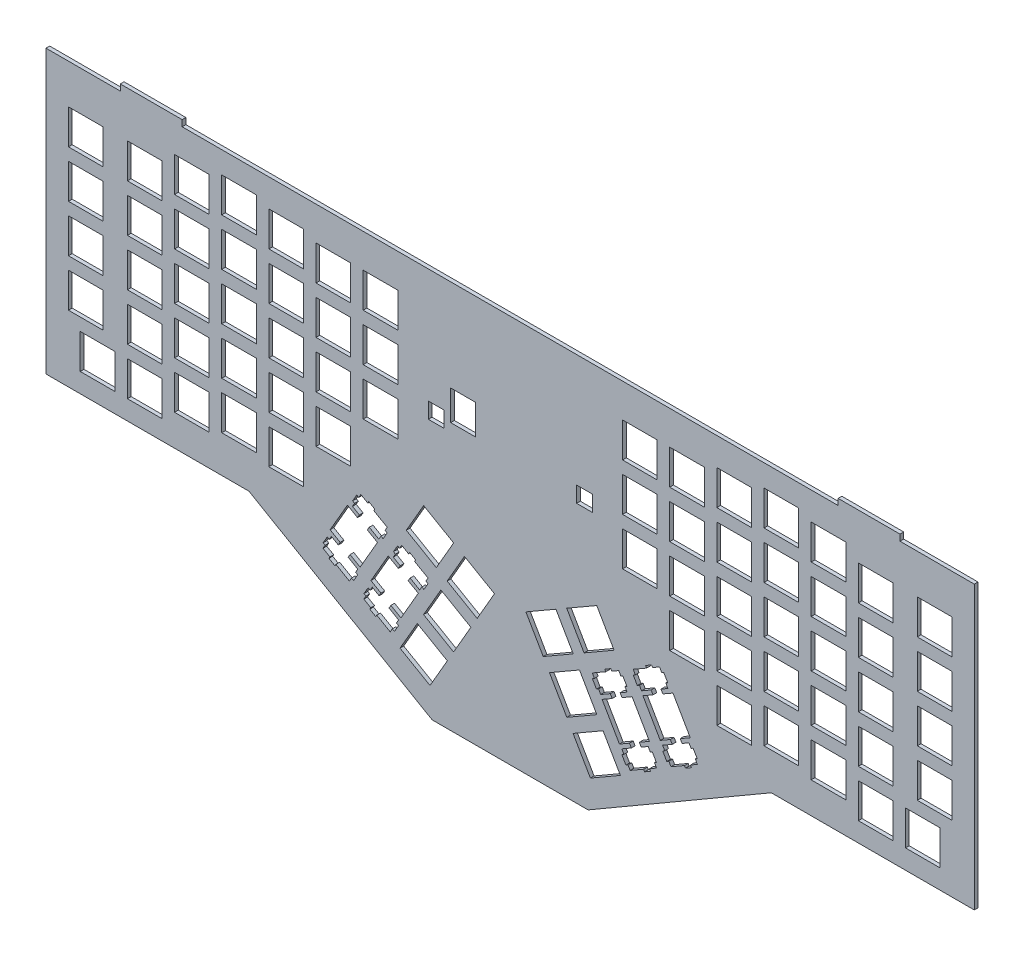
SolidWorks part; units mm, degrees
ref_plane "Front Plane" through (0, 0, 0) normal (0, 0, 1) x (1, 0, 0)
ref_plane "Top Plane" through (0, 0, 0) normal (0, 1, 0) x (1, 0, 0)
ref_plane "Right Plane" through (0, 0, 0) normal (1, 0, 0) x (0, 0, -1)
sketch "Model" plane through (0, 0, 0) normal (0, 0, 1) x (1, 0, 0)
  line L0 (0.0951, 142.78) -> (371.57, 142.78)
  line L1 (371.57, 142.78) -> (371.57, 0.2467)
  line L2 (371.57, 0.2467) -> (0.0951, 0.2467)
  line L3 (0.0951, 0.2467) -> (0.0951, 142.78)
  line L4 (141.314, 10.6977) -> (153.439, 3.6973)
  line L5 (153.439, 3.6973) -> (160.438, 15.8213)
  line L6 (160.438, 15.8213) -> (148.314, 22.8217)
  line L7 (148.314, 22.8217) -> (141.314, 10.6977)
  line L8 (211.224, 15.8213) -> (218.225, 3.6973)
  line L9 (218.225, 3.6973) -> (230.35, 10.6977)
  line L10 (230.35, 10.6977) -> (223.35, 22.8217)
  line L11 (223.35, 22.8217) -> (211.224, 15.8213)
  line L12 (141.126, 45.533) -> (140.33, 45.992)
  line L13 (140.33, 45.992) -> (138.679, 43.1341)
  line L14 (138.679, 43.1341) -> (139.477, 42.6752)
  line L15 (139.477, 42.6752) -> (138.614, 41.1812)
  line L16 (138.614, 41.1812) -> (141.412, 39.5661)
  line L17 (141.412, 39.5661) -> (140.648, 38.2461)
  line L18 (140.648, 38.2461) -> (136.579, 40.5955)
  line L19 (136.579, 40.5955) -> (129.578, 28.4716)
  line L20 (129.578, 28.4716) -> (133.649, 26.1221)
  line L21 (133.649, 26.1221) -> (132.887, 24.8006)
  line L22 (132.887, 24.8006) -> (130.09, 26.4156)
  line L23 (130.09, 26.4156) -> (129.227, 24.9218)
  line L24 (129.227, 24.9218) -> (128.429, 25.3821)
  line L25 (128.429, 25.3821) -> (126.78, 22.524)
  line L26 (126.78, 22.524) -> (127.576, 22.0638)
  line L27 (127.576, 22.0638) -> (126.715, 20.57)
  line L28 (126.715, 20.57) -> (129.512, 18.9549)
  line L29 (129.512, 18.9549) -> (129.099, 18.2411)
  line L30 (129.099, 18.2411) -> (131.524, 16.841)
  line L31 (131.524, 16.841) -> (131.936, 17.5548)
  line L32 (131.936, 17.5548) -> (137.367, 14.4198)
  line L33 (137.367, 14.4198) -> (138.228, 15.9136)
  line L34 (138.228, 15.9136) -> (139.077, 15.423)
  line L35 (139.077, 15.423) -> (140.728, 18.2811)
  line L36 (140.728, 18.2811) -> (139.879, 18.773)
  line L37 (139.879, 18.773) -> (140.742, 20.2654)
  line L38 (140.742, 20.2654) -> (136.871, 22.5006)
  line L39 (136.871, 22.5006) -> (137.633, 23.8221)
  line L40 (137.633, 23.8221) -> (141.702, 21.4712)
  line L41 (141.702, 21.4712) -> (148.703, 33.5952)
  line L42 (148.703, 33.5952) -> (144.632, 35.9463)
  line L43 (144.632, 35.9463) -> (145.396, 37.2664)
  line L44 (145.396, 37.2664) -> (149.266, 35.0311)
  line L45 (149.266, 35.0311) -> (150.129, 36.5248)
  line L46 (150.129, 36.5248) -> (150.978, 36.0345)
  line L47 (150.978, 36.0345) -> (152.628, 38.8923)
  line L48 (152.628, 38.8923) -> (151.778, 39.3831)
  line L49 (151.778, 39.3831) -> (152.641, 40.8767)
  line L50 (152.641, 40.8767) -> (147.212, 44.0119)
  line L51 (147.212, 44.0119) -> (147.624, 44.7269)
  line L52 (147.624, 44.7269) -> (145.198, 46.1271)
  line L53 (145.198, 46.1271) -> (144.786, 45.412)
  line L54 (144.786, 45.412) -> (141.989, 47.027)
  line L55 (141.989, 47.027) -> (141.126, 45.533)
  line L56 (226.876, 45.412) -> (226.464, 46.1271)
  line L57 (226.464, 46.1271) -> (224.04, 44.7269)
  line L58 (224.04, 44.7269) -> (224.452, 44.0119)
  line L59 (224.452, 44.0119) -> (219.021, 40.8767)
  line L60 (219.021, 40.8767) -> (219.884, 39.3831)
  line L61 (219.884, 39.3831) -> (219.035, 38.8923)
  line L62 (219.035, 38.8923) -> (220.686, 36.0345)
  line L63 (220.686, 36.0345) -> (221.535, 36.5248)
  line L64 (221.535, 36.5248) -> (222.396, 35.0311)
  line L65 (222.396, 35.0311) -> (226.267, 37.2664)
  line L66 (226.267, 37.2664) -> (227.031, 35.9463)
  line L67 (227.031, 35.9463) -> (222.961, 33.5952)
  line L68 (222.961, 33.5952) -> (229.96, 21.4712)
  line L69 (229.96, 21.4712) -> (234.031, 23.8221)
  line L70 (234.031, 23.8221) -> (234.793, 22.5006)
  line L71 (234.793, 22.5006) -> (230.922, 20.2654)
  line L72 (230.922, 20.2654) -> (231.785, 18.773)
  line L73 (231.785, 18.773) -> (230.936, 18.2811)
  line L74 (230.936, 18.2811) -> (232.585, 15.423)
  line L75 (232.585, 15.423) -> (233.434, 15.9136)
  line L76 (233.434, 15.9136) -> (234.297, 14.4198)
  line L77 (234.297, 14.4198) -> (239.726, 17.5548)
  line L78 (239.726, 17.5548) -> (240.14, 16.841)
  line L79 (240.14, 16.841) -> (242.565, 18.2411)
  line L80 (242.565, 18.2411) -> (242.152, 18.9549)
  line L81 (242.152, 18.9549) -> (244.949, 20.57)
  line L82 (244.949, 20.57) -> (244.086, 22.0638)
  line L83 (244.086, 22.0638) -> (244.883, 22.524)
  line L84 (244.883, 22.524) -> (243.233, 25.3821)
  line L85 (243.233, 25.3821) -> (242.437, 24.9218)
  line L86 (242.437, 24.9218) -> (241.573, 26.4156)
  line L87 (241.573, 26.4156) -> (238.777, 24.8006)
  line L88 (238.777, 24.8006) -> (238.014, 26.1221)
  line L89 (238.014, 26.1221) -> (242.084, 28.4716)
  line L90 (242.084, 28.4716) -> (235.085, 40.5955)
  line L91 (235.085, 40.5955) -> (231.014, 38.2461)
  line L92 (231.014, 38.2461) -> (230.251, 39.5661)
  line L93 (230.251, 39.5661) -> (233.048, 41.1812)
  line L94 (233.048, 41.1812) -> (232.187, 42.6752)
  line L95 (232.187, 42.6752) -> (232.984, 43.1341)
  line L96 (232.984, 43.1341) -> (231.334, 45.992)
  line L97 (231.334, 45.992) -> (230.536, 45.533)
  line L98 (230.536, 45.533) -> (229.674, 47.027)
  line L99 (229.674, 47.027) -> (226.876, 45.412)
  line L100 (150.839, 27.1942) -> (162.964, 20.1952)
  line L101 (162.964, 20.1952) -> (169.963, 32.3191)
  line L102 (169.963, 32.3191) -> (157.839, 39.3196)
  line L103 (157.839, 39.3196) -> (150.839, 27.1942)
  line L104 (201.699, 32.3191) -> (208.7, 20.1952)
  line L105 (208.7, 20.1952) -> (220.825, 27.1942)
  line L106 (220.825, 27.1942) -> (213.825, 39.3196)
  line L107 (213.825, 39.3196) -> (201.699, 32.3191)
  line L108 (124.627, 55.058) -> (123.832, 55.517)
  line L109 (123.832, 55.517) -> (122.182, 52.6591)
  line L110 (122.182, 52.6591) -> (122.979, 52.2002)
  line L111 (122.979, 52.2002) -> (122.116, 50.7062)
  line L112 (122.116, 50.7062) -> (124.912, 49.0911)
  line L113 (124.912, 49.0911) -> (124.15, 47.7711)
  line L114 (124.15, 47.7711) -> (120.081, 50.1206)
  line L115 (120.081, 50.1206) -> (113.08, 37.9966)
  line L116 (113.08, 37.9966) -> (117.151, 35.6471)
  line L117 (117.151, 35.6471) -> (116.389, 34.3256)
  line L118 (116.389, 34.3256) -> (113.592, 35.9406)
  line L119 (113.592, 35.9406) -> (112.729, 34.4468)
  line L120 (112.729, 34.4468) -> (111.933, 34.9071)
  line L121 (111.933, 34.9071) -> (110.283, 32.0491)
  line L122 (110.283, 32.0491) -> (111.078, 31.5888)
  line L123 (111.078, 31.5888) -> (110.217, 30.095)
  line L124 (110.217, 30.095) -> (113.013, 28.4799)
  line L125 (113.013, 28.4799) -> (112.601, 27.7661)
  line L126 (112.601, 27.7661) -> (115.025, 26.366)
  line L127 (115.025, 26.366) -> (115.438, 27.0798)
  line L128 (115.438, 27.0798) -> (120.869, 23.9448)
  line L129 (120.869, 23.9448) -> (121.731, 25.4386)
  line L130 (121.731, 25.4386) -> (122.579, 24.948)
  line L131 (122.579, 24.948) -> (124.229, 27.806)
  line L132 (124.229, 27.806) -> (123.38, 28.2966)
  line L133 (123.38, 28.2966) -> (124.244, 29.7904)
  line L134 (124.244, 29.7904) -> (120.373, 32.0256)
  line L135 (120.373, 32.0256) -> (121.135, 33.3471)
  line L136 (121.135, 33.3471) -> (125.204, 30.9962)
  line L137 (125.204, 30.9962) -> (132.205, 43.12)
  line L138 (132.205, 43.12) -> (128.134, 45.4713)
  line L139 (128.134, 45.4713) -> (128.898, 46.7914)
  line L140 (128.898, 46.7914) -> (132.769, 44.5562)
  line L141 (132.769, 44.5562) -> (133.631, 46.0498)
  line L142 (133.631, 46.0498) -> (134.48, 45.5595)
  line L143 (134.48, 45.5595) -> (136.13, 48.4173)
  line L144 (136.13, 48.4173) -> (135.281, 48.9081)
  line L145 (135.281, 48.9081) -> (136.143, 50.4017)
  line L146 (136.143, 50.4017) -> (130.714, 53.5368)
  line L147 (130.714, 53.5368) -> (131.126, 54.2519)
  line L148 (131.126, 54.2519) -> (128.702, 55.6521)
  line L149 (128.702, 55.6521) -> (128.288, 54.937)
  line L150 (128.288, 54.937) -> (125.491, 56.552)
  line L151 (125.491, 56.552) -> (124.627, 55.058)
  line L152 (243.374, 54.937) -> (242.962, 55.6521)
  line L153 (242.962, 55.6521) -> (240.538, 54.2519)
  line L154 (240.538, 54.2519) -> (240.95, 53.5368)
  line L155 (240.95, 53.5368) -> (235.519, 50.4017)
  line L156 (235.519, 50.4017) -> (236.383, 48.9081)
  line L157 (236.383, 48.9081) -> (235.533, 48.4173)
  line L158 (235.533, 48.4173) -> (237.184, 45.5595)
  line L159 (237.184, 45.5595) -> (238.033, 46.0498)
  line L160 (238.033, 46.0498) -> (238.894, 44.5562)
  line L161 (238.894, 44.5562) -> (242.765, 46.7914)
  line L162 (242.765, 46.7914) -> (243.528, 45.4713)
  line L163 (243.528, 45.4713) -> (239.457, 43.12)
  line L164 (239.457, 43.12) -> (246.458, 30.9962)
  line L165 (246.458, 30.9962) -> (250.527, 33.3471)
  line L166 (250.527, 33.3471) -> (251.291, 32.0256)
  line L167 (251.291, 32.0256) -> (247.42, 29.7904)
  line L168 (247.42, 29.7904) -> (248.283, 28.2966)
  line L169 (248.283, 28.2966) -> (247.434, 27.806)
  line L170 (247.434, 27.806) -> (249.083, 24.948)
  line L171 (249.083, 24.948) -> (249.932, 25.4386)
  line L172 (249.932, 25.4386) -> (250.795, 23.9448)
  line L173 (250.795, 23.9448) -> (256.224, 27.0798)
  line L174 (256.224, 27.0798) -> (256.638, 26.366)
  line L175 (256.638, 26.366) -> (259.062, 27.7661)
  line L176 (259.062, 27.7661) -> (258.65, 28.4799)
  line L177 (258.65, 28.4799) -> (261.447, 30.095)
  line L178 (261.447, 30.095) -> (260.584, 31.5888)
  line L179 (260.584, 31.5888) -> (261.381, 32.0491)
  line L180 (261.381, 32.0491) -> (259.73, 34.9071)
  line L181 (259.73, 34.9071) -> (258.935, 34.4468)
  line L182 (258.935, 34.4468) -> (258.072, 35.9406)
  line L183 (258.072, 35.9406) -> (255.275, 34.3256)
  line L184 (255.275, 34.3256) -> (254.51, 35.6471)
  line L185 (254.51, 35.6471) -> (258.582, 37.9966)
  line L186 (258.582, 37.9966) -> (251.583, 50.1206)
  line L187 (251.583, 50.1206) -> (247.512, 47.7711)
  line L188 (247.512, 47.7711) -> (246.75, 49.0911)
  line L189 (246.75, 49.0911) -> (249.546, 50.7062)
  line L190 (249.546, 50.7062) -> (248.685, 52.2002)
  line L191 (248.685, 52.2002) -> (249.48, 52.6591)
  line L192 (249.48, 52.6591) -> (247.831, 55.517)
  line L193 (247.831, 55.517) -> (247.034, 55.058)
  line L194 (247.034, 55.058) -> (246.172, 56.552)
  line L195 (246.172, 56.552) -> (243.374, 54.937)
  line L196 (160.364, 43.6922) -> (172.489, 36.6931)
  line L197 (172.489, 36.6931) -> (179.488, 48.817)
  line L198 (179.488, 48.817) -> (167.364, 55.8176)
  line L199 (167.364, 55.8176) -> (160.364, 43.6922)
  line L200 (192.174, 48.817) -> (199.175, 36.6931)
  line L201 (199.175, 36.6931) -> (211.3, 43.6922)
  line L202 (211.3, 43.6922) -> (204.3, 55.8176)
  line L203 (204.3, 55.8176) -> (192.174, 48.817)
  line L204 (12.1447, 56.9129) -> (26.1441, 56.9129)
  line L205 (26.1441, 56.9129) -> (26.1441, 42.9122)
  line L206 (26.1441, 42.9122) -> (12.1447, 42.9122)
  line L207 (12.1447, 42.9122) -> (12.1447, 56.9129)
  line L208 (31.1947, 56.9129) -> (45.194, 56.9129)
  line L209 (45.194, 56.9129) -> (45.194, 42.9122)
  line L210 (45.194, 42.9122) -> (31.1947, 42.9122)
  line L211 (31.1947, 42.9122) -> (31.1947, 56.9129)
  line L212 (326.47, 56.9129) -> (340.469, 56.9129)
  line L213 (340.469, 56.9129) -> (340.469, 42.9122)
  line L214 (340.469, 42.9122) -> (326.47, 42.9122)
  line L215 (326.47, 42.9122) -> (326.47, 56.9129)
  line L216 (345.52, 56.9129) -> (359.519, 56.9129)
  line L217 (359.519, 56.9129) -> (359.519, 42.9122)
  line L218 (359.519, 42.9122) -> (345.52, 42.9122)
  line L219 (345.52, 42.9122) -> (345.52, 56.9129)
  line L220 (143.866, 53.2172) -> (155.991, 46.2181)
  line L221 (155.991, 46.2181) -> (162.99, 58.342)
  line L222 (162.99, 58.342) -> (150.865, 65.3426)
  line L223 (150.865, 65.3426) -> (143.866, 53.2172)
  line L224 (208.672, 58.342) -> (215.672, 46.2181)
  line L225 (215.672, 46.2181) -> (227.798, 53.2172)
  line L226 (227.798, 53.2172) -> (220.798, 65.3426)
  line L227 (220.798, 65.3426) -> (208.672, 58.342)
  line L228 (50.2447, 61.674) -> (64.244, 61.674)
  line L229 (64.244, 61.674) -> (64.244, 47.6747)
  line L230 (64.244, 47.6747) -> (50.2447, 47.6747)
  line L231 (50.2447, 47.6747) -> (50.2447, 61.674)
  line L232 (88.3447, 61.674) -> (102.344, 61.674)
  line L233 (102.344, 61.674) -> (102.344, 47.6747)
  line L234 (102.344, 47.6747) -> (88.3447, 47.6747)
  line L235 (88.3447, 47.6747) -> (88.3447, 61.674)
  line L236 (269.32, 61.674) -> (283.319, 61.674)
  line L237 (283.319, 61.674) -> (283.319, 47.6747)
  line L238 (283.319, 47.6747) -> (269.32, 47.6747)
  line L239 (269.32, 47.6747) -> (269.32, 61.674)
  line L240 (307.42, 61.674) -> (321.419, 61.674)
  line L241 (321.419, 61.674) -> (321.419, 47.6747)
  line L242 (321.419, 47.6747) -> (307.42, 47.6747)
  line L243 (307.42, 47.6747) -> (307.42, 61.674)
  line L244 (69.2947, 64.0553) -> (83.294, 64.0553)
  line L245 (83.294, 64.0553) -> (83.294, 50.056)
  line L246 (83.294, 50.056) -> (69.2947, 50.056)
  line L247 (69.2947, 50.056) -> (69.2947, 64.0553)
  line L248 (288.37, 64.0553) -> (302.369, 64.0553)
  line L249 (302.369, 64.0553) -> (302.369, 50.056)
  line L250 (302.369, 50.056) -> (288.37, 50.056)
  line L251 (288.37, 50.056) -> (288.37, 64.0553)
  line L252 (7.3822, 75.9629) -> (21.3817, 75.9629)
  line L253 (21.3817, 75.9629) -> (21.3817, 61.9622)
  line L254 (21.3817, 61.9622) -> (7.3822, 61.9622)
  line L255 (7.3822, 61.9622) -> (7.3822, 75.9629)
  line L256 (31.1947, 75.9629) -> (45.194, 75.9629)
  line L257 (45.194, 75.9629) -> (45.194, 61.9622)
  line L258 (45.194, 61.9622) -> (31.1947, 61.9622)
  line L259 (31.1947, 61.9622) -> (31.1947, 75.9629)
  line L260 (326.47, 75.9629) -> (340.469, 75.9629)
  line L261 (340.469, 75.9629) -> (340.469, 61.9622)
  line L262 (340.469, 61.9622) -> (326.47, 61.9622)
  line L263 (326.47, 61.9622) -> (326.47, 75.9629)
  line L264 (350.282, 75.9629) -> (364.282, 75.9629)
  line L265 (364.282, 75.9629) -> (364.282, 61.9622)
  line L266 (364.282, 61.9622) -> (350.282, 61.9622)
  line L267 (350.282, 61.9622) -> (350.282, 75.9629)
  line L268 (107.395, 78.3428) -> (121.394, 78.3428)
  line L269 (121.394, 78.3428) -> (121.394, 64.3435)
  line L270 (121.394, 64.3435) -> (107.395, 64.3435)
  line L271 (107.395, 64.3435) -> (107.395, 78.3428)
  line L272 (250.27, 78.3428) -> (264.269, 78.3428)
  line L273 (264.269, 78.3428) -> (264.269, 64.3435)
  line L274 (264.269, 64.3435) -> (250.27, 64.3435)
  line L275 (250.27, 64.3435) -> (250.27, 78.3428)
  line L276 (50.2447, 80.724) -> (64.244, 80.724)
  line L277 (64.244, 80.724) -> (64.244, 66.7247)
  line L278 (64.244, 66.7247) -> (50.2447, 66.7247)
  line L279 (50.2447, 66.7247) -> (50.2447, 80.724)
  line L280 (88.3447, 80.724) -> (102.344, 80.724)
  line L281 (102.344, 80.724) -> (102.344, 66.7247)
  line L282 (102.344, 66.7247) -> (88.3447, 66.7247)
  line L283 (88.3447, 66.7247) -> (88.3447, 80.724)
  line L284 (269.32, 80.724) -> (283.319, 80.724)
  line L285 (283.319, 80.724) -> (283.319, 66.7247)
  line L286 (283.319, 66.7247) -> (269.32, 66.7247)
  line L287 (269.32, 66.7247) -> (269.32, 80.724)
  line L288 (307.42, 80.724) -> (321.419, 80.724)
  line L289 (321.419, 80.724) -> (321.419, 66.7247)
  line L290 (321.419, 66.7247) -> (307.42, 66.7247)
  line L291 (307.42, 66.7247) -> (307.42, 80.724)
  line L292 (69.2947, 83.1053) -> (83.294, 83.1053)
  line L293 (83.294, 83.1053) -> (83.294, 69.106)
  line L294 (83.294, 69.106) -> (69.2947, 69.106)
  line L295 (69.2947, 69.106) -> (69.2947, 83.1053)
  line L296 (288.37, 83.1053) -> (302.369, 83.1053)
  line L297 (302.369, 83.1053) -> (302.369, 69.106)
  line L298 (302.369, 69.106) -> (288.37, 69.106)
  line L299 (288.37, 69.106) -> (288.37, 83.1053)
  line L300 (7.3822, 95.0129) -> (21.3817, 95.0129)
  line L301 (21.3817, 95.0129) -> (21.3817, 81.0122)
  line L302 (21.3817, 81.0122) -> (7.3822, 81.0122)
  line L303 (7.3822, 81.0122) -> (7.3822, 95.0129)
  line L304 (31.1947, 95.0129) -> (45.194, 95.0129)
  line L305 (45.194, 95.0129) -> (45.194, 81.0122)
  line L306 (45.194, 81.0122) -> (31.1947, 81.0122)
  line L307 (31.1947, 81.0122) -> (31.1947, 95.0129)
  line L308 (326.47, 95.0129) -> (340.469, 95.0129)
  line L309 (340.469, 95.0129) -> (340.469, 81.0122)
  line L310 (340.469, 81.0122) -> (326.47, 81.0122)
  line L311 (326.47, 81.0122) -> (326.47, 95.0129)
  line L312 (350.282, 95.0129) -> (364.282, 95.0129)
  line L313 (364.282, 95.0129) -> (364.282, 81.0122)
  line L314 (364.282, 81.0122) -> (350.282, 81.0122)
  line L315 (350.282, 81.0122) -> (350.282, 95.0129)
  line L316 (107.395, 97.3928) -> (121.394, 97.3928)
  line L317 (121.394, 97.3928) -> (121.394, 83.3935)
  line L318 (121.394, 83.3935) -> (107.395, 83.3935)
  line L319 (107.395, 83.3935) -> (107.395, 97.3928)
  line L320 (126.445, 97.3928) -> (140.444, 97.3928)
  line L321 (140.444, 97.3928) -> (140.444, 83.3935)
  line L322 (140.444, 83.3935) -> (126.445, 83.3935)
  line L323 (126.445, 83.3935) -> (126.445, 97.3928)
  line L324 (231.22, 97.3928) -> (245.219, 97.3928)
  line L325 (245.219, 97.3928) -> (245.219, 83.3935)
  line L326 (245.219, 83.3935) -> (231.22, 83.3935)
  line L327 (231.22, 83.3935) -> (231.22, 97.3928)
  line L328 (250.27, 97.3928) -> (264.269, 97.3928)
  line L329 (264.269, 97.3928) -> (264.269, 83.3935)
  line L330 (264.269, 83.3935) -> (250.27, 83.3935)
  line L331 (250.27, 83.3935) -> (250.27, 97.3928)
  line L332 (50.2447, 99.774) -> (64.244, 99.774)
  line L333 (64.244, 99.774) -> (64.244, 85.7747)
  line L334 (64.244, 85.7747) -> (50.2447, 85.7747)
  line L335 (50.2447, 85.7747) -> (50.2447, 99.774)
  line L336 (88.3447, 99.774) -> (102.344, 99.774)
  line L337 (102.344, 99.774) -> (102.344, 85.7747)
  line L338 (102.344, 85.7747) -> (88.3447, 85.7747)
  line L339 (88.3447, 85.7747) -> (88.3447, 99.774)
  line L340 (269.32, 99.774) -> (283.319, 99.774)
  line L341 (283.319, 99.774) -> (283.319, 85.7747)
  line L342 (283.319, 85.7747) -> (269.32, 85.7747)
  line L343 (269.32, 85.7747) -> (269.32, 99.774)
  line L344 (307.42, 99.774) -> (321.419, 99.774)
  line L345 (321.419, 99.774) -> (321.419, 85.7747)
  line L346 (321.419, 85.7747) -> (307.42, 85.7747)
  line L347 (307.42, 85.7747) -> (307.42, 99.774)
  line L348 (69.2947, 102.155) -> (83.294, 102.155)
  line L349 (83.294, 102.155) -> (83.294, 88.156)
  line L350 (83.294, 88.156) -> (69.2947, 88.156)
  line L351 (69.2947, 88.156) -> (69.2947, 102.155)
  line L352 (288.37, 102.155) -> (302.369, 102.155)
  line L353 (302.369, 102.155) -> (302.369, 88.156)
  line L354 (302.369, 88.156) -> (288.37, 88.156)
  line L355 (288.37, 88.156) -> (288.37, 102.155)
  line L356 (7.3822, 114.063) -> (21.3817, 114.063)
  line L357 (21.3817, 114.063) -> (21.3817, 100.062)
  line L358 (21.3817, 100.062) -> (7.3822, 100.062)
  line L359 (7.3822, 100.062) -> (7.3822, 114.063)
  line L360 (31.1947, 114.063) -> (45.194, 114.063)
  line L361 (45.194, 114.063) -> (45.194, 100.062)
  line L362 (45.194, 100.062) -> (31.1947, 100.062)
  line L363 (31.1947, 100.062) -> (31.1947, 114.063)
  line L364 (326.47, 114.063) -> (340.469, 114.063)
  line L365 (340.469, 114.063) -> (340.469, 100.062)
  line L366 (340.469, 100.062) -> (326.47, 100.062)
  line L367 (326.47, 100.062) -> (326.47, 114.063)
  line L368 (350.282, 114.063) -> (364.282, 114.063)
  line L369 (364.282, 114.063) -> (364.282, 100.062)
  line L370 (364.282, 100.062) -> (350.282, 100.062)
  line L371 (350.282, 100.062) -> (350.282, 114.063)
  line L372 (107.395, 116.443) -> (121.394, 116.443)
  line L373 (121.394, 116.443) -> (121.394, 102.443)
  line L374 (121.394, 102.443) -> (107.395, 102.443)
  line L375 (107.395, 102.443) -> (107.395, 116.443)
  line L376 (126.445, 116.443) -> (140.444, 116.443)
  line L377 (140.444, 116.443) -> (140.444, 102.443)
  line L378 (140.444, 102.443) -> (126.445, 102.443)
  line L379 (126.445, 102.443) -> (126.445, 116.443)
  line L380 (231.22, 116.443) -> (245.219, 116.443)
  line L381 (245.219, 116.443) -> (245.219, 102.443)
  line L382 (245.219, 102.443) -> (231.22, 102.443)
  line L383 (231.22, 102.443) -> (231.22, 116.443)
  line L384 (250.27, 116.443) -> (264.269, 116.443)
  line L385 (264.269, 116.443) -> (264.269, 102.443)
  line L386 (264.269, 102.443) -> (250.27, 102.443)
  line L387 (250.27, 102.443) -> (250.27, 116.443)
  line L388 (50.2447, 118.824) -> (64.244, 118.824)
  line L389 (64.244, 118.824) -> (64.244, 104.825)
  line L390 (64.244, 104.825) -> (50.2447, 104.825)
  line L391 (50.2447, 104.825) -> (50.2447, 118.824)
  line L392 (88.3447, 118.824) -> (102.344, 118.824)
  line L393 (102.344, 118.824) -> (102.344, 104.825)
  line L394 (102.344, 104.825) -> (88.3447, 104.825)
  line L395 (88.3447, 104.825) -> (88.3447, 118.824)
  line L396 (269.32, 118.824) -> (283.319, 118.824)
  line L397 (283.319, 118.824) -> (283.319, 104.825)
  line L398 (283.319, 104.825) -> (269.32, 104.825)
  line L399 (269.32, 104.825) -> (269.32, 118.824)
  line L400 (307.42, 118.824) -> (321.419, 118.824)
  line L401 (321.419, 118.824) -> (321.419, 104.825)
  line L402 (321.419, 104.825) -> (307.42, 104.825)
  line L403 (307.42, 104.825) -> (307.42, 118.824)
  line L404 (69.2947, 121.205) -> (83.294, 121.205)
  line L405 (83.294, 121.205) -> (83.294, 107.206)
  line L406 (83.294, 107.206) -> (69.2947, 107.206)
  line L407 (69.2947, 107.206) -> (69.2947, 121.205)
  line L408 (288.37, 121.205) -> (302.369, 121.205)
  line L409 (302.369, 121.205) -> (302.369, 107.206)
  line L410 (302.369, 107.206) -> (288.37, 107.206)
  line L411 (288.37, 107.206) -> (288.37, 121.205)
  line L412 (7.3822, 133.113) -> (21.3817, 133.113)
  line L413 (21.3817, 133.113) -> (21.3817, 119.112)
  line L414 (21.3817, 119.112) -> (7.3822, 119.112)
  line L415 (7.3822, 119.112) -> (7.3822, 133.113)
  line L416 (31.1947, 133.113) -> (45.194, 133.113)
  line L417 (45.194, 133.113) -> (45.194, 119.112)
  line L418 (45.194, 119.112) -> (31.1947, 119.112)
  line L419 (31.1947, 119.112) -> (31.1947, 133.113)
  line L420 (326.47, 133.113) -> (340.469, 133.113)
  line L421 (340.469, 133.113) -> (340.469, 119.112)
  line L422 (340.469, 119.112) -> (326.47, 119.112)
  line L423 (326.47, 119.112) -> (326.47, 133.113)
  line L424 (350.282, 133.113) -> (364.282, 133.113)
  line L425 (364.282, 133.113) -> (364.282, 119.112)
  line L426 (364.282, 119.112) -> (350.282, 119.112)
  line L427 (350.282, 119.112) -> (350.282, 133.113)
  line L428 (107.395, 135.493) -> (121.394, 135.493)
  line L429 (121.394, 135.493) -> (121.394, 121.493)
  line L430 (121.394, 121.493) -> (107.395, 121.493)
  line L431 (107.395, 121.493) -> (107.395, 135.493)
  line L432 (126.445, 135.493) -> (140.444, 135.493)
  line L433 (140.444, 135.493) -> (140.444, 121.493)
  line L434 (140.444, 121.493) -> (126.445, 121.493)
  line L435 (126.445, 121.493) -> (126.445, 135.493)
  line L436 (231.22, 135.493) -> (245.219, 135.493)
  line L437 (245.219, 135.493) -> (245.219, 121.493)
  line L438 (245.219, 121.493) -> (231.22, 121.493)
  line L439 (231.22, 121.493) -> (231.22, 135.493)
  line L440 (250.27, 135.493) -> (264.269, 135.493)
  line L441 (264.269, 135.493) -> (264.269, 121.493)
  line L442 (264.269, 121.493) -> (250.27, 121.493)
  line L443 (250.27, 121.493) -> (250.27, 135.493)
  line L444 (50.2447, 137.874) -> (64.244, 137.874)
  line L445 (64.244, 137.874) -> (64.244, 123.875)
  line L446 (64.244, 123.875) -> (50.2447, 123.875)
  line L447 (50.2447, 123.875) -> (50.2447, 137.874)
  line L448 (88.3447, 137.874) -> (102.344, 137.874)
  line L449 (102.344, 137.874) -> (102.344, 123.875)
  line L450 (102.344, 123.875) -> (88.3447, 123.875)
  line L451 (88.3447, 123.875) -> (88.3447, 137.874)
  line L452 (269.32, 137.874) -> (283.319, 137.874)
  line L453 (283.319, 137.874) -> (283.319, 123.875)
  line L454 (283.319, 123.875) -> (269.32, 123.875)
  line L455 (269.32, 123.875) -> (269.32, 137.874)
  line L456 (307.42, 137.874) -> (321.419, 137.874)
  line L457 (321.419, 137.874) -> (321.419, 123.875)
  line L458 (321.419, 123.875) -> (307.42, 123.875)
  line L459 (307.42, 123.875) -> (307.42, 137.874)
  line L460 (69.2947, 140.255) -> (83.294, 140.255)
  line L461 (83.294, 140.255) -> (83.294, 126.256)
  line L462 (83.294, 126.256) -> (69.2947, 126.256)
  line L463 (69.2947, 126.256) -> (69.2947, 140.255)
  line L464 (288.37, 140.255) -> (302.369, 140.255)
  line L465 (302.369, 140.255) -> (302.369, 126.256)
  line L466 (302.369, 126.256) -> (288.37, 126.256)
  line L467 (288.37, 126.256) -> (288.37, 140.255)
extrude "Boss-Extrude1" add sketch "Model" along normal blind 1.5
sketch "Sketch1" plane through (0, 142.78, 0) normal (0, 1, 0) x (1, 0, 0)
  line L0 (0.0951, 0) -> (0.0951, -1.5)
  line L1 (0.0951, -1.5) -> (371.57, -1.5)
  line L2 (371.57, -1.5) -> (371.57, 0)
  line L3 (371.57, 0) -> (0.0951, 0)
  line L4 (0.0951, -1.5) -> (0.0951, 0) construction
extrude "Boss-Extrude2" add sketch "Sketch1" along normal blind 5.46
sketch "Sketch2" plane through (0, 0.2467, 0) normal (0, -1, 0) x (1, 0, 0)
  line L0 (0.0951, 1.5) -> (0.0951, 0)
  line L1 (0.0951, 0) -> (371.57, 0)
  line L2 (371.57, 0) -> (371.57, 1.5)
  line L3 (371.57, 1.5) -> (0.0951, 1.5)
extrude "Boss-Extrude3" add sketch "Sketch2" along normal blind 8.2
sketch "Sketch6" plane through (371.57, 0, 0) normal (1, 0, 0) x (0, 0, -1)
  line L0 (-1.5, -7.9533) -> (0, -7.9533)
  line L1 (0, -7.9533) -> (0, 148.24)
  line L2 (0, 148.24) -> (-1.5, 148.24)
  line L3 (-1.5, 148.24) -> (-1.5, -7.9533)
extrude "Boss-Extrude5" add sketch "Sketch6" along normal blind 2
sketch "Sketch9" plane through (0.0951, 0, 0) normal (-1, 0, 0) x (0, 0, 1)
  line L0 (0, -7.9533) -> (1.5, -7.9533)
  line L1 (1.5, -7.9533) -> (1.5, 148.24)
  line L2 (1.5, 148.24) -> (0, 148.24)
  line L4 (0, 148.24) -> (0, -7.9533)
extrude "Boss-Extrude8" add sketch "Sketch9" along normal blind 10
sketch "Sketch7" plane through (0, 148.24, 0) normal (0, 1, 0) x (1, 0, 0)
  line L0 (-9.9049, 0) -> (-9.9049, -1.5)
  line L1 (-9.9049, -1.5) -> (373.57, -1.5)
  line L2 (373.57, -1.5) -> (373.57, 0)
  line L3 (373.57, 0) -> (-9.9049, 0)
  line L4 (373.57, 0) -> (-9.9049, 0) construction
extrude "Boss-Extrude9" add sketch "Sketch7" along normal blind 10
sketch "Sketch10" plane through (0, 0, 0) normal (0, 0, -1) x (-1, 0, 0)
  line L9 (9.9049, -7.9533) -> (9.9049, 158.24)
  line L10 (9.9049, 158.24) -> (-373.57, 158.24)
  line L11 (-373.57, 158.24) -> (-373.57, 149.0988)
  line L12 (-373.57, -7.9533) -> (-373.57, 158.24) construction
  line L13 (-373.57, 149.0988) -> (-373.3117, 149.0988) construction
  line L14 (-373.3117, 149.0988) -> (1.6883, 149.0988)
  line L15 (9.9049, -7.9533) -> (-373.57, -7.9533) construction
  line L17 (1.6883, 149.0988) -> (1.6883, 35.0988)
  line L18 (1.6883, 35.0988) -> (-80.3117, 35.0988)
  line L19 (-80.3117, 35.0988) -> (-154.3117, -7.9012)
  line L20 (-154.3117, -7.9012) -> (-154.3117, -7.9533) construction
  line L21 (-154.3117, -7.9533) -> (9.9049, -7.9533)
  line L22 (-154.3117, -7.9533) -> (-373.57, -7.9533)
  line L23 (-373.57, -7.9533) -> (-373.57, 149.0988)
  line L24 (-373.3117, 149.0988) -> (-373.3117, 35.0988)
  line L25 (-373.3117, 35.0988) -> (-291.3117, 35.0988)
  line L26 (-291.3117, 35.0988) -> (-217.3117, -7.9012)
  line L27 (-291.3117, 35.0988) -> (-217.3117, -7.9012) construction
  line L28 (-217.3117, -7.9012) -> (-154.3117, -7.9012) construction
  line L29 (-217.3117, -7.9012) -> (-154.3117, -7.9012)
extrude "Cut-Extrude1" cut sketch "Sketch10" against normal blind 10
sketch "Sketch4" plane through (0, 0, 1.5) normal (0, 0, 1) x (1, 0, 0)
  line L0 (158.9617, 99.6888) -> (159.1617, 99.6888) construction
  line L1 (152.7617, 102.8888) -> (159.1617, 102.8888)
  line L2 (152.7617, 102.8888) -> (152.7617, 96.4888)
  line L3 (152.7617, 96.4888) -> (159.1617, 96.4888)
  line L4 (159.1617, 102.8888) -> (159.1617, 96.4888)
  line L5 (155.9617, 96.4888) -> (155.9617, 102.8888) construction
  line L6 (152.7617, 99.6888) -> (159.1617, 99.6888) construction
  line L7 (218.8617, 100.2388) -> (219.0617, 100.2388) construction
  line L8 (155.9617, 102.6888) -> (155.9617, 102.8888) construction
  line L9 (218.8617, 97.5388) -> (218.8617, 102.9388) construction
  line L10 (165.7807, 109.9588) -> (167.8127, 109.9588) construction
  line L11 (166.7967, 109.9588) -> (166.7967, 111.9588) construction
  line L12 (161.7967, 111.9588) -> (171.7967, 111.9588)
  line L13 (161.7967, 111.9588) -> (161.7967, 99.8388)
  line L14 (161.7967, 99.8388) -> (171.7967, 99.8388)
  line L15 (171.7967, 111.9588) -> (171.7967, 99.8388)
  line L16 (161.7967, 111.9588) -> (171.7967, 99.8388) construction
  line L17 (161.7967, 99.8388) -> (171.7967, 111.9588) construction
  line L18 (166.7967, 102.3388) -> (166.7967, 99.8388) construction
  line L19 (215.8617, 103.2388) -> (215.8617, 103.4432) construction
  line L20 (212.6617, 103.4432) -> (219.0617, 103.4432)
  line L21 (212.6617, 103.4432) -> (212.6617, 97.0344)
  line L22 (212.6617, 97.0344) -> (219.0617, 97.0344)
  line L23 (219.0617, 103.4432) -> (219.0617, 97.0344)
  line L24 (212.6617, 103.4432) -> (219.0617, 97.0344) construction
  line L25 (212.6617, 97.0344) -> (219.0617, 103.4432) construction
  line L26 (218.5617, 103.2388) -> (213.1617, 103.2388) construction
  line L27 (158.9617, 96.9888) -> (158.9617, 102.3888) construction
  line L30 (158.6617, 102.6888) -> (153.2617, 102.6888) construction
  point P12 (166.7967, 105.8988)
  point P21 (215.8617, 100.2388)
  point P152 (155.9617, 99.6888)
  dimension "D1" = 0.2
  dimension "D2" = 0.2
  dimension "D3" = 2
  dimension "D4" = 2.5
  dimension "D5" = 10
  dimension "D6" = 0.2
  dimension "D7" = 0.2044
extrude "Cut-Extrude2" cut sketch "Sketch4" against normal blind 2
sketch "Sketch11" plane through (0, 149.0988, 0) normal (0, 1, 0) x (1, 0, 0)
  line L0 (-1.6883, 0) -> (28.3117, 0) construction
  line L1 (-1.6883, 0) -> (373.3117, 0) construction
  line L2 (28.3117, 0) -> (28.3117, -1.5)
  line L3 (-1.6883, -1.5) -> (373.3117, -1.5) construction
  line L4 (28.3117, -1.5) -> (53.3117, -1.5)
  line L5 (53.3117, -1.5) -> (53.3117, 0)
  line L6 (53.3117, 0) -> (28.3117, 0)
  line L7 (373.3117, 0) -> (343.3117, 0) construction
  line L8 (373.3117, -1.5) -> (373.3117, 0) construction
  line L9 (343.3117, 0) -> (343.3117, -1.5)
  line L10 (343.3117, -1.5) -> (318.3117, -1.5)
  line L11 (318.3117, -1.5) -> (318.3117, 0)
  line L12 (318.3117, 0) -> (343.3117, 0)
  dimension "D1" = 30
  dimension "D2" = 25
  dimension "D3" = 30
  dimension "D4" = 25
extrude "Boss-Extrude10" add sketch "Sketch11" along normal blind 2.5
equation "\"tab_offset\"= 30"
equation "\"D3@Sketch11\"=\"tab_offset\""
equation "\"tab_width\"=25"
equation "\"D4@Sketch11\"=\"tab_width\""
equation "\"D1@Sketch11\"=\"tab_offset\""
equation "\"D2@Sketch11\"=\"tab_width\""
equation "\"tab_depth\"=2.5"
equation "\"D1@Boss-Extrude10\"=\"tab_depth\""
